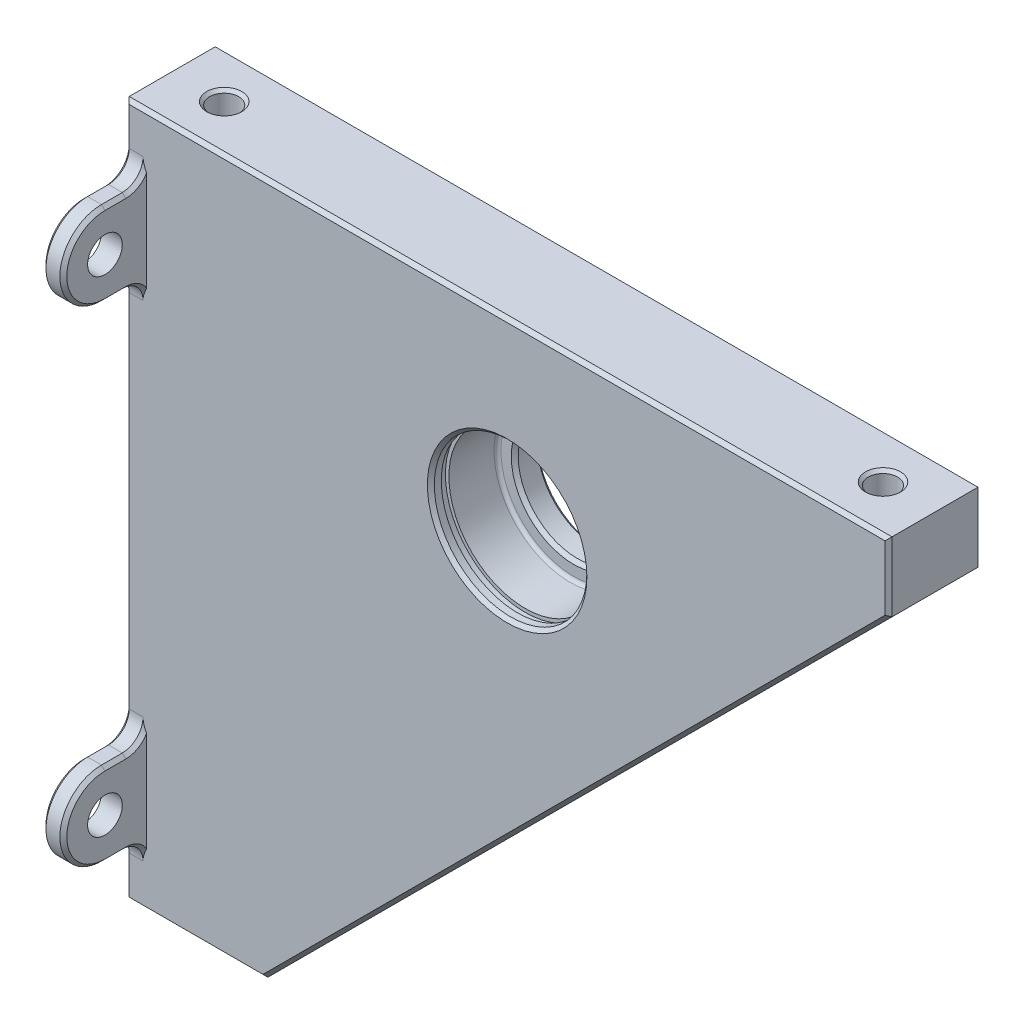
SolidWorks part; units mm, degrees
material "1.0503 (C45)"
ref_plane "Front Plane" through (0, 0, 0) normal (0, 0, 1) x (1, 0, 0)
ref_plane "Top Plane" through (0, 0, 0) normal (0, 1, 0) x (1, 0, 0)
ref_plane "Right Plane" through (0, 0, 0) normal (1, 0, 0) x (0, 0, -1)
sketch "Sketch1" plane through (0, 0, 0) normal (0, 0, 1) x (1, 0, 0)
  line L0 (0, 0) -> (20, 0)
  line L1 (20, 0) -> (110, 90)
  line L2 (110, 90) -> (110, 100)
  line L3 (110, 100) -> (0, 100)
  line L4 (0, 100) -> (0, 0)
  dimension "D1" = 45
  dimension "D2" = 100
  dimension "D3" = 20
  dimension "D4" = 110
extrude "Boss-Extrude1" add sketch "Sketch1" along normal blind 13.4
sketch "Sketch3" plane through (0, 0, 0) normal (-1, 0, 0) x (0, 0, 1)
  line L0 (13.4, 100) -> (13.4, 0) construction
  line L1 (13.4, 91) -> (19.4, 91)
  line L2 (13.4, 79) -> (19.4, 79)
  line L3 (13.4, 21) -> (19.4, 21)
  line L4 (13.4, 9) -> (19.4, 9)
  line L5 (0, 91) -> (-6, 91)
  line L6 (0, 100) -> (0, 0) construction
  line L7 (0, 79) -> (-6, 79)
  line L8 (0, 21) -> (-6, 21)
  line L9 (0, 9) -> (-6, 9)
  line L10 (0, 91) -> (0, 79)
  line L11 (13.4, 100) -> (0, 100) construction
  line L12 (13.4, 0) -> (0, 0) construction
  line L13 (13.4, 91) -> (13.4, 79)
  line L14 (13.4, 21) -> (13.4, 9)
  line L15 (0, 21) -> (0, 9)
  arc A0 (-6, 91) -> (-6, 79) centre (-6, 85) ccw
  arc A1 (-6, 21) -> (-6, 9) centre (-6, 15) ccw
  arc A2 (19.4, 91) -> (19.4, 79) centre (19.4, 85) cw
  arc A3 (19.4, 21) -> (19.4, 9) centre (19.4, 15) cw
  dimension "D1" = 15
  dimension "D3" = 6
  dimension "D8" = 6
  dimension "D10" = 6
  dimension "D2" = 6
  dimension "D4" = 15
  dimension "D5" = 6
  dimension "D6" = 6
  dimension "D7" = 6
  dimension "D9" = 15
  dimension "D11" = 15
extrude "Boss-Extrude2" add sketch "Sketch3" against normal blind 3
fillet "Fillet1" radius 3 8 edges at (1.5, 79, 13.4) (1.5, 91, 13.4) (1.5, 21, 13.4) (1.5, 9, 13.4) (1.5, 21, 0) (1.5, 9, 0) (1.5, 91, 0) (1.5, 79, 0)
chamfer "Chamfer1" distance 0.5 angle 45 54 edges at (3, 91.8787, -0.8787) (3, 91, -4.5) (3, 85, -12) (3, 79, -4.5) (3, 78.1213, -0.8787) (0, 50, 0) (3, 21.8787, -0.8787) (3, 21, -4.5) (3, 15, -12) (3, 9, -4.5) (3, 8.1213, -0.8787) (0, 78.1213, -0.8787) (0, 21.8787, -0.8787) (0, 79, -4.5) (0, 21, -4.5) (0, 85, -12) (0, 15, -12) (0, 91, -4.5) (0, 9, -4.5) (0, 91.8787, -0.8787) (0, 8.1213, -0.8787) (0, 97, 0) (0, 3, 0) (10, 0, 0) (65, 45, 0) (110, 95, 0) (55, 100, 0) (3, 8.1213, 14.2787) (3, 9, 17.9) (3, 15, 25.4) (3, 21, 17.9) (3, 21.8787, 14.2787) (0, 50, 13.4) (3, 78.1213, 14.2787) (3, 79, 17.9) (3, 85, 25.4) (3, 91, 17.9) (3, 91.8787, 14.2787) (0, 21.8787, 14.2787) (0, 78.1213, 14.2787) (0, 21, 17.9) (0, 79, 17.9) (0, 15, 25.4) (0, 85, 25.4) (0, 9, 17.9) (0, 91, 17.9) (0, 8.1213, 14.2787) (0, 91.8787, 14.2787) (0, 3, 13.4) (10, 0, 13.4) (65, 45, 13.4) (110, 95, 13.4) (55, 100, 13.4) (0, 97, 13.4)
hole_wizard "Ø5.0mm Dowel Hole1" positions "Sketch4" profile "Sketch5" hole size "Ø5.0" standard "DIN" end condition through all
sketch "Sketch4" plane through (3, 0, 0) normal (1, 0, 0) x (0, 0, -1)
  point P0 (-19.4, 85)
  point P3 (-19.4, 15)
  point P6 (6, 15)
  point P9 (6, 85)
sketch "Sketch5" plane through (3, 85, 19.4) normal (0, 1, 0) x (0, 0, -1)
  line L0 (0, 0) -> (0, 3)
  line L1 (0, 3) -> (2.5, 3)
  line L2 (2.5, 3) -> (2.5, 0)
  line L5 (2.5, 0) -> (0, 0)
  line L11 (0, -6.35) -> (0, 107.95) construction
  dimension "Thru Hole Dia." = 5
  dimension "Thru Hole Depth" = 3
ref_plane "Plane1" through (55, 0, 0) normal (1, 0, 0) x (0, 0, -1)
sketch "Sketch7" plane through (55, 0, 0) normal (1, 0, 0) x (0, 0, -1)
  line L1 (-13.4, 76) -> (-13.4, 24) construction
  line L2 (-13.4, 84.5) -> (-11.9, 84.5)
  line L3 (-11.9, 84.5) -> (-11.9, 85)
  line L4 (-11.9, 85) -> (-10.8, 85)
  line L5 (-10.8, 85) -> (-10.8, 84.5)
  line L6 (-10.8, 84.5) -> (-4.3, 84.5)
  line L11 (0, 24) -> (0, 76) construction
  line L12 (-13.4, 84.5) -> (-13.4, 73.5)
  line L13 (-13.4, 73.5) -> (0, 73.5)
  line L14 (0, 73.5) -> (0, 82)
  line L15 (-3.8, 84) -> (-3.8, 82)
  line L16 (-3.8, 82) -> (0, 82)
  line L17 (-32.6, 153.5) -> (-54.6, 153.5) construction
  line L18 (-13.4, 0.5) -> (-13.4, 90.2071) construction
  arc A0 (-4.3, 84.5) -> (-3.8, 84) centre (-4.3, 84) cw
  dimension "D1" = 0.5
  dimension "D2" = 8.5
  dimension "D3" = 1.5
  dimension "D4" = 7
  dimension "D5" = 1.1
  dimension "D6" = 11
  dimension "D7" = 11.5
  dimension "D8" = 80
revolve "Cut-Revolve1" cut sketch "Sketch7" angle 360 about L13
chamfer "Fase1" distance 0.5 angle 45 3 edges at (66, 73.5, 13.4) (63.5, 73.5, 0) (63.5, 73.5, 3.8)
hole_wizard "M5 Tapped Hole1" positions "Skizze1" profile "Skizze2" tap size "M5" standard "DIN"
sketch "Skizze1" plane through (0, 100, 0) normal (0, 1, 0) x (1, 0, 0)
  arc A1 (102.5, -4.2) -> (102.5, -9.2) centre (102.5, -6.7) ccw construction
  arc A5 (7.5, -9.2) -> (7.5, -4.2) centre (7.5, -6.7) ccw construction
  point P0 (7.5, -6.7)
  point P2 (102.5, -6.7)
  point P23 (7.5, -6.7)
  point P26 (102.5, -6.7)
  point P28 (7.5, -6.7)
  point P30 (102.5, -6.7)
sketch "Skizze2" plane through (7.5, 100, 6.7) normal (1, 0, 0) x (0, 0, 1)
  line L0 (0, 0) -> (0, 11.2618)
  line L1 (0, 11.2618) -> (2.1, 10)
  line L2 (2.1, 10) -> (2.1, 0.428)
  line L3 (2.1, 0.428) -> (2.528, 0)
  line L5 (2.528, 0) -> (0, 0)
  line L6 (-2.1, 0.428) -> (-2.528, 0) construction
  line L10 (0, 11.2618) -> (-2.1, 10) construction
  line L11 (0, -6.35) -> (0, 107.95) construction
  dimension "Tap Drill Dia." = 4.2
  dimension "Tap Drill Depth" = 10
  dimension "Near C'Sink Dia." = 5.056
  dimension "Near C'Sink Angle" = 90
  dimension "Drill Angle" = 118
